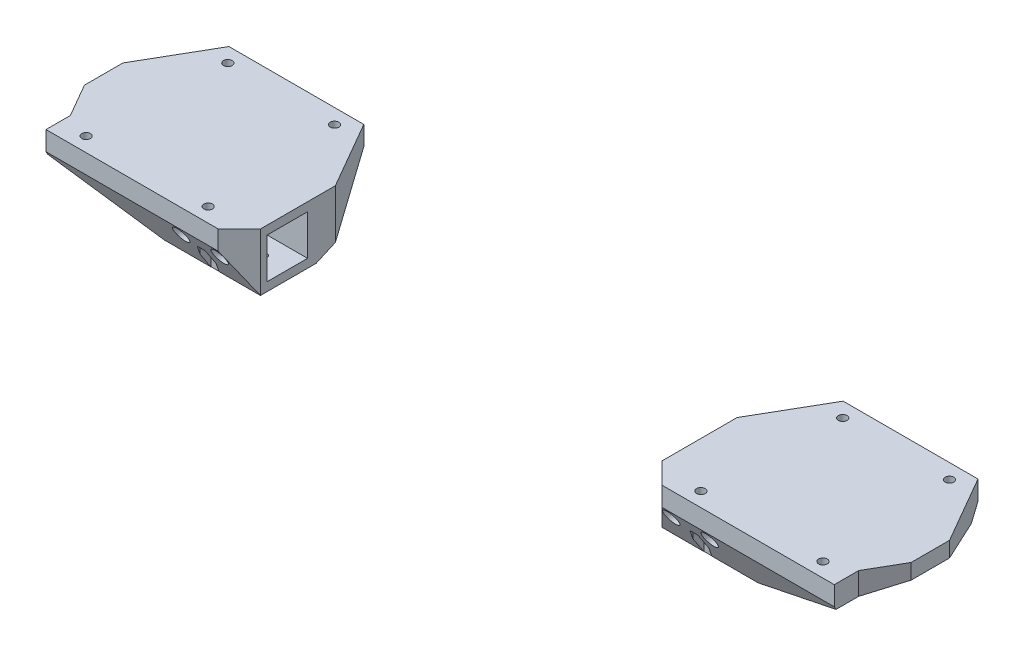
SolidWorks part; units mm, degrees
note: '?' marks a value the reader was unsure of. The reader was unsure of these and kept them because the rebuilt part matched: shared geometry of "Sketch5<4>", "Sketch7<3>".
material "PET"
ref_plane "Front Plane" through (0, 0, 0) normal (0, 0, 1) x (1, 0, 0)
ref_plane "Top Plane" through (0, 0, 0) normal (0, 1, 0) x (1, 0, 0)
ref_plane "Right Plane" through (0, 0, 0) normal (1, 0, 0) x (0, 0, -1)
ref_plane "Plane1" through (0, 0, 0) normal (0, 0, 1) x (1, 0, 0)
sketch "Sketch1" plane through (0, 0, 0) normal (0, 0, 1) x (1, 0, 0)
  line L0 (-104.5375, 610) -> (-215.1276, 610)
  line L1 (-215.1276, 610) -> (-215.1276, 602)
  line L2 (-215.1276, 602) -> (-154.5375, 580)
  line L3 (-154.5375, 580) -> (-104.5375, 580)
  line L4 (-104.5375, 580) -> (-104.5375, 610)
  dimension "D1" = 8
  dimension "D2" = 30
  dimension "D3" = 50
extrude "Boss-Extrude1" add sketch "Sketch1" along normal blind 35 and the other way blind 50
sketch "Sketch2" plane through (0, 610, 0) normal (0, 1, 0) x (1, 0, 0)
  line L4 (-215.1276, 15) -> (-194.9203, 50)
  line L5 (-215.1276, 50) -> (-215.1276, -35) construction
  line L6 (-104.5375, 50) -> (-215.1276, 50) construction
  line L7 (-194.9203, 50) -> (-215.1276, 50)
  line L8 (-215.1276, 50) -> (-215.1276, 15)
  line L9 (-159.8325, -35) -> (-159.8325, 50) construction
  line L10 (-104.5375, -35) -> (-215.1276, -35) construction
  line L11 (-205.1276, -22.3205) -> (-215.1276, -5)
  line L12 (-215.1276, -5) -> (-215.1276, -35)
  line L13 (-215.1276, -35) -> (-205.1276, -35)
  line L14 (-205.1276, -35) -> (-205.1276, -22.3205)
  line L16 (-104.5375, 50) -> (-104.5375, -35) construction
  line L18 (-115.5375, -35) -> (-104.5375, -35)
  line L19 (-104.5375, -35) -> (-104.5375, -24)
  line L20 (-104.5375, 50) -> (-104.5375, 15)
  line L21 (-124.7448, 50) -> (-104.5375, 50)
  line L22 (-104.5375, 15) -> (-124.7448, 50)
  line L23 (-104.5375, -24) -> (-115.5375, -35)
  dimension "D1" = 30
  dimension "D2" = 35
  dimension "D3" = 30
  dimension "D4" = 10
  dimension "D5" = 30
  dimension "D6" = 11
  dimension "D7" = 11
extrude "Cut-Extrude1" cut sketch "Sketch2" against normal blind 35
sketch "Sketch3" plane through (0, 0, 0) normal (1, 0, 0) x (0, 0, -1)
  line L0 (50, 600) -> (5, 580)
  line L1 (50, 610) -> (50, 580) construction
  line L2 (15, 580) -> (-24, 580) construction
  line L3 (5, 580) -> (50, 580)
  line L4 (50, 580) -> (50, 600)
  line L5 (-24, 580) -> (-35, 600)
  line L6 (-35, 610) -> (-35, 580) construction
  line L7 (-35, 600) -> (-35, 580)
  line L8 (-35, 580) -> (-24, 580)
  dimension "D1" = 20
  dimension "D2" = 45
extrude "Cut-Extrude2" cut sketch "Sketch3" against normal blind 215
sketch "Sketch4" plane through (-104.5375, 0, 0) normal (1, 0, 0) x (0, 0, -1)
  line L1 (0.5, 584.5) -> (-20.5, 584.5)
  line L2 (0.5, 584.5) -> (0.5, 605.5)
  line L3 (0.5, 605.5) -> (-20.5, 605.5)
  line L4 (-20.5, 584.5) -> (-20.5, 605.5)
  line L5 (0.5, 584.5) -> (-20.5, 605.5) construction
  line L6 (0.5, 605.5) -> (-20.5, 584.5) construction
  point P0 (-10, 595)
  dimension "D1" = 21
  dimension "D2" = 21
extrude "Cut-Extrude3" cut sketch "Sketch4" against normal blind 46
ref_plane "Plane2" through (0, 600, 0) normal (0, 1, 0) x (1, 0, 0)
sketch "Sketch5" plane through (0, 600, 0) normal (0, 1, 0) x (1, 0, 0)
  line L1 (-191.9334, 42.275) -> (-189.855, 38.675)
  line L2 (-189.855, 38.675) -> (-185.698, 38.675)
  line L3 (-185.698, 38.675) -> (-183.6196, 42.275)
  line L4 (-183.6196, 42.275) -> (-185.698, 45.875)
  line L5 (-185.698, 45.875) -> (-189.855, 45.875)
  line L6 (-189.855, 45.875) -> (-191.9334, 42.275)
  line L7 (-195.9069, -27.5) -> (-193.8285, -31.1)
  line L8 (-193.8285, -31.1) -> (-189.6715, -31.1)
  line L9 (-189.6715, -31.1) -> (-187.5931, -27.5)
  line L10 (-187.5931, -27.5) -> (-189.6715, -23.9)
  line L11 (-189.6715, -23.9) -> (-193.8285, -23.9)
  line L12 (-193.8285, -23.9) -> (-195.9069, -27.5)
  line L13 (-132.4069, -27.5) -> (-130.3285, -31.1)
  line L14 (-130.3285, -31.1) -> (-126.1715, -31.1)
  line L15 (-126.1715, -31.1) -> (-124.0931, -27.5)
  line L16 (-124.0931, -27.5) -> (-126.1715, -23.9)
  line L17 (-126.1715, -23.9) -> (-130.3285, -23.9)
  line L18 (-130.3285, -23.9) -> (-132.4069, -27.5)
  line L19 (-128.0666, 42.275) -> (-130.145, 45.875)
  line L20 (-130.145, 45.875) -> (-134.302, 45.875)
  line L21 (-134.302, 45.875) -> (-136.3804, 42.275)
  line L22 (-136.3804, 42.275) -> (-134.302, 38.675)
  line L23 (-134.302, 38.675) -> (-130.145, 38.675)
  line L24 (-130.145, 38.675) -> (-128.0666, 42.275)
  circle A0 centre (-132.2235, 42.275) radius 2.25
  circle A1 centre (-187.7765, 42.275) radius 2.25
  circle A2 centre (-191.75, -27.5) radius 2.25
  circle A3 centre (-128.25, -27.5) radius 2.25
  circle A4 centre (-187.7765, 42.275) radius 3.6 construction
  circle A5 centre (-191.75, -27.5) radius 3.6 construction
  circle A6 centre (-128.25, -27.5) radius 3.6 construction
  circle A7 centre (-132.2235, 42.275) radius 3.6 construction
  dimension "D1" = 4.5
  dimension "D2" = 7.2
extrude "Cut-Extrude4" cut sketch "Sketch5" against normal blind 46 contours A0 | L23 L24 L19 L20 L21 L22 A0 | A1 | L5 L6 L1 L2 L3 L4 A1 | A2 | L11 L12 L7 L8 L9 L10 A2 | A3 | L17 L18 L13 L14 L15 L16 A3
extrude "Cut-Extrude5" cut sketch "Sketch5<4>" along normal blind 46 contours A0 | A1 | A2 | A3
sketch "Sketch5<4>" plane through (0, 600, 0) normal (0, 1, 0) x (1, 0, 0) same geometry as "Sketch5"
sketch "Sketch6" plane through (0, 584.5, 0) normal (0, 1, 0) x (1, 0, 0)
  line L0 (-150.5375, -10) -> (-104.5375, -10) construction
  line L1 (-150.5375, 0.5) -> (-150.5375, -20.5) construction
  line L2 (-104.5375, 15) -> (-104.5375, -24) construction
  line L3 (-137.5375, -10) -> (-117.5375, -10) construction
  circle A0 centre (-137.5375, -10) radius 2.25
  circle A1 centre (-117.5375, -10) radius 2.25
  point P10 (-127.5375, -10)
  dimension "D1" = 4.5
  dimension "D2" = 20
extrude "Cut-Extrude6" cut sketch "Sketch6" against normal blind 10
sketch "Sketch7" plane through (0, 0, 20.5) normal (0, 0, -1) x (-1, 0, 0)
  line L0 (150.5375, 595) -> (104.5375, 595) construction
  line L1 (150.5375, 584.5) -> (150.5375, 605.5) construction
  line L2 (104.5375, 584.4444) -> (104.5375, 610) construction
  line L3 (117.5375, 595) -> (137.5375, 595)
  circle A0 centre (117.5375, 595) radius 2.25
  circle A1 centre (137.5375, 595) radius 2.25
  circle A2 centre (117.5375, 595) radius 4
  circle A3 centre (137.5375, 595) radius 4
  point P8 (127.5375, 595)
  dimension "D2" = 4.5
  dimension "D3" = 8
  dimension "D1" = 20
extrude "Cut-Extrude7" cut sketch "Sketch7" against normal blind 20 contours L0 L3 A0 | L0 A0 L3 A2 | A0 L0 A2 L3 | L3 L0 A0 | A1 L0 L3 | A3 L0 A1 L3 | L0 A1 L3 | L0 A3 L3 A1
extrude "Boss-Extrude2" add sketch "Sketch7<3>" against normal blind 5 contours L0 A0 L3 A2 | A0 L0 A2 L3 | A3 L0 A1 L3 | L0 A3 L3 A1 | L0 A1 L3 | A1 L0 L3
sketch "Sketch7<3>" plane through (0, 0, 20.5) normal (0, 0, -1) x (-1, 0, 0) same geometry as "Sketch7"
sketch "Sketch8" plane through (0, 580, 0) normal (0, -1, 0) x (1, 0, 0)
  line L6 (-193.1754, -43.0223) -> (-192.0336, -45)
  line L8 (-109.5375, -13.6603) -> (-109.5375, -10)
  line L9 (-109.5375, -13.6603) -> (-109.5375, -10)
  line L14 (-196.7152, 18.9) -> (-200.1276, 24.8104)
  line L16 (-200.1276, 24.8104) -> (-200.1276, 20.9808)
  line L20 (-192.7417, -50.875) -> (-182.8113, -50.875)
  line L21 (-182.8113, -50.875) -> (-177.8461, -42.275)
  line L22 (-177.8461, -42.275) -> (-182.8113, -33.675)
  line L23 (-182.8113, -33.675) -> (-192.7417, -33.675)
  line L24 (-192.7417, -33.675) -> (-197.7069, -42.275)
  line L25 (-197.7069, -42.275) -> (-192.7417, -50.875)
  line L26 (-152.7547, -10) -> (-193.1754, -43.0223)
  line L27 (-192.0336, -45) -> (-127.6315, -45)
  line L28 (-183.4504, 24.6753) -> (-186.7848, 18.9)
  line L29 (-186.7848, 18.9) -> (-196.7152, 18.9)
  line L30 (-200.1276, 20.9808) -> (-210.1276, 3.6603)
  line L31 (-210.1276, 3.6603) -> (-210.1276, -13.6603)
  line L32 (-210.1276, -13.6603) -> (-198.2412, -34.248)
  line L33 (-198.2412, -34.248) -> (-159.5375, -2.6284)
  line L34 (-159.5375, -2.6284) -> (-159.5375, 19.8998)
  line L35 (-159.5375, 19.8998) -> (-183.4504, 24.6753)
  line L36 (-183.4504, 24.6753) -> (-186.7848, 18.9)
  line L37 (-186.7848, 18.9) -> (-201.3289, 18.9)
  line L38 (-201.3289, 18.9) -> (-210.1276, 3.6603)
  line L39 (-210.1276, 3.6603) -> (-210.1276, -13.6603)
  line L40 (-210.1276, -13.6603) -> (-198.2412, -34.248)
  line L41 (-198.2412, -34.248) -> (-159.5375, -2.6284)
  line L42 (-159.5375, -2.6284) -> (-159.5375, 19.8998)
  line L43 (-159.5375, 19.8998) -> (-183.4504, 24.6753)
  line L44 (-127.6315, -45) -> (-109.5375, -13.6603)
  line L45 (-109.5375, -10) -> (-152.7547, -10)
  line L46 (-152.7547, -10) -> (-182.466, -34.2731)
  line L47 (-176.2728, -45) -> (-143.7272, -45)
  line L48 (-121.093, -33.675) -> (-109.5375, -13.6603)
  line L49 (-109.5375, -10) -> (-152.7547, -10)
  line L52 (-176.2728, -45) -> (-182.466, -34.2731)
  line L84 (-127.2583, -33.675) -> (-137.1887, -33.675)
  line L85 (-137.1887, -33.675) -> (-142.1539, -42.275)
  line L86 (-142.1539, -42.275) -> (-137.1887, -50.875)
  line L87 (-137.1887, -50.875) -> (-127.2583, -50.875)
  line L88 (-127.2583, -50.875) -> (-122.2931, -42.275)
  line L89 (-122.2931, -42.275) -> (-127.2583, -33.675)
  line L90 (-121.093, -33.675) -> (-137.1887, -33.675)
  line L91 (-137.1887, -33.675) -> (-143.7272, -45)
  dimension "D1" = 5
  dimension "D2" = 5
  dimension "D3" = 5
  dimension "D4" = 5
wrap "Wrap1" [suppressed] sketch "Sketch8" source sketch "Sketch8" thickness 5 parameters "D1"=5
chamfer "Chamfer2" [suppressed] distance 5 angle 45
ref_plane "Plane3" through (-0.0375, 0, 0) normal (1, 0, 0) x (0, 0, -1)
ref_plane "Plane4" through (0, 292.5, -292.5) normal (0, -0.7071, 0.7071) x (-1, 0, 0)
ref_plane "Plane5" through (0, 302.5, 302.5) normal (0, -0.7071, -0.7071) x (1, 0, 0)
ref_axis "Axis1" through (-82.0283, 595, 10) along (-1, 0, 0)?
other "Graphic1" [suppressed]
other "Graphic (Closed) -1"
ref_plane "Plane6" through (-89.5167, 0, 76.3686) normal (0.7608, 0, -0.649) x (-0.649, 0, -0.7608)
ref_plane "Plane7" through (-95.6883, 0, -81.6337) normal (-0.7608, 0, -0.649) x (-0.649, 0, 0.7608)
ref_axis "Axis2" through (-160, 591.2599, -6.2496) along (0, 1, 0)?
other "Graphic2" [suppressed]
other "Graphic (Closed) -2"
mirror "Mirror2" about plane through (-0.0375, 0, 0) normal (1, 0, 0) of bodies 109
